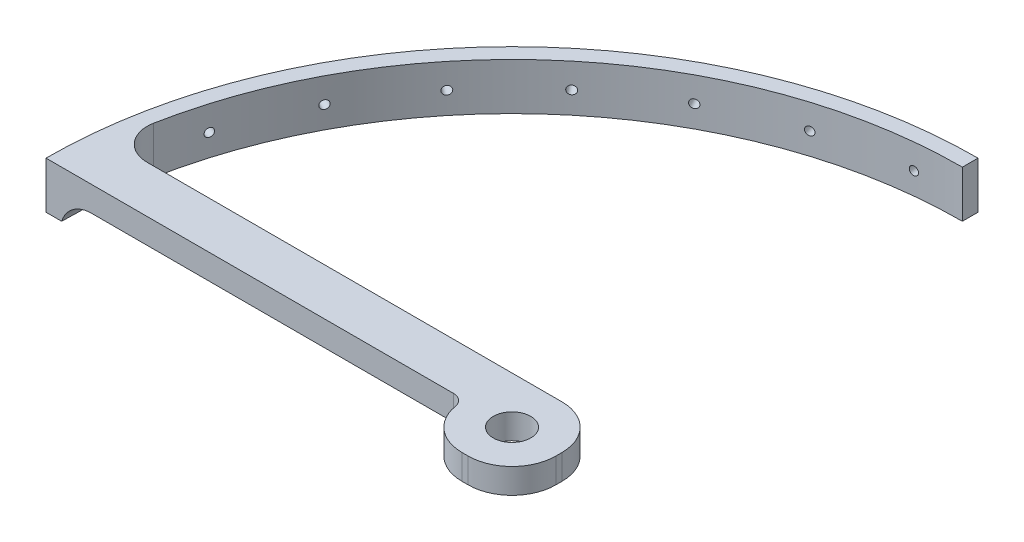
SolidWorks part; units mm, degrees
ref_plane "Front Plane" through (0, 0, 0) normal (0, 0, 1) x (1, 0, 0)
ref_plane "Top Plane" through (0, 0, 0) normal (0, 1, 0) x (1, 0, 0)
ref_plane "Right Plane" through (0, 0, 0) normal (1, 0, 0) x (0, 0, -1)
sketch "Sketch1" plane through (0, 0, 0) normal (0, 1, 0) x (1, 0, 0)
  line L0 (0, 0) -> (-149, 0) construction
  line L1 (0, 0) -> (0, 149) construction
  line L2 (0, 144) -> (0, 149)
  line L3 (-149, 0) -> (-144, 0)
  line L4 (-144, 0) -> (15, 0) construction
  line L5 (15, 0) -> (15, 1)
  line L6 (1, 15) -> (-131.6473, 15)
  line L7 (15, 0) -> (15, -1)
  line L8 (1, -15) -> (-1, -15)
  line L9 (-15, -1) -> (-15, 0)
  line L10 (-18.7482, 0) -> (-144, 0)
  arc A0 (0, 149) -> (-149, 0) centre (0, 0) ccw
  arc A1 (0, 144) -> (-141.4717, 26.8657) centre (0, 0) ccw
  circle A2 centre (0, 0) radius 144 construction
  circle A3 centre (0, 0) radius 149 construction
  arc A4 (1, 15) -> (15, 1) centre (1, 1) cw
  arc A5 (15, -1) -> (1, -15) centre (1, -1) cw
  arc A6 (-1, -15) -> (-14.8042, -3.3333) centre (-1, -1) cw
  arc A7 (-14.8042, -3.3333) -> (-18.7482, 0) centre (-18.7482, -4) ccw
  arc A8 (-141.4717, 26.8657) -> (-131.6473, 15) centre (-131.6473, 25) ccw
  circle A9 centre (0, 0) radius 6
  point P19 (15, -15)
  dimension "D1" = 298
  dimension "D3" = 149
  dimension "D8" = 14
  dimension "D9" = 4
  dimension "D10" = 10
  dimension "D11" = 12
  dimension "D4" = 159
  dimension "D5" = 15
  dimension "D6" = 30
  dimension "D7" = 15
  dimension "D2" = 5
extrude "Boss-Extrude1" add sketch "Sketch1" along normal blind 8 contours A8 A1 L2 A0 L3 L10 A7 A6 L8 A5 L7 L5 A4 L6 A9 region at (-93.3141, 0, -112.7023)
sketch "Sketch3" plane through (0, 0, 0) normal (0, -1, 0) x (1, 0, 0)
  line L0 (-149, 0) -> (-18.7482, 0) construction
  line L1 (-149, 0) -> (-144, 0)
  line L2 (0, -149) -> (0, -144)
  arc A1 (-149, 0) -> (0, -149) centre (0, 0) ccw
  arc A2 (-149, 0) -> (0, -149) centre (0, 0) ccw construction
  arc A3 (-144, 0) -> (0, -144) centre (0, 0) ccw
  dimension "D1" = 5
extrude "Boss-Extrude2" add sketch "Sketch3" along normal blind 7
fillet "Fillet1" radius 10 1 edges at (-143.3665, 0, -13.4922)
sketch "Sketch4" plane through (0, 0, 0) normal (0, -1, 0) x (-1, 0, 0)
  line L0 (0, 0) -> (143.3665, 13.4922) construction
  arc A0 (144, 0) -> (141.4717, 26.8657) centre (0, 0) ccw construction
ref_plane "Plane1" through (-148.3445, 0, -13.9607) normal (-0.9956, 0, -0.0937) x (-0.0937, 0, 0.9956)
sketch "Sketch5" plane through (-148.3445, 0, -13.9607) normal (-0.9956, 0, -0.0937) x (-0.0937, 0, 0.9956)
  circle A0 centre (0, 0) radius 1.35
  dimension "D1" = 2.7
extrude "Cut-Extrude1" cut sketch "Sketch5" against normal blind 10
sketch "Sketch6" plane through (0, 0, 0) normal (0, 0, 1) x (1, 0, 0)
  line L0 (0, 0) -> (0, -61.317) construction
pattern_circular "CirPattern2" count 32 over 360 about axis through (0, 0, 0) along (0, -1, 0) of "Cut-Extrude1" reverse direction yes
